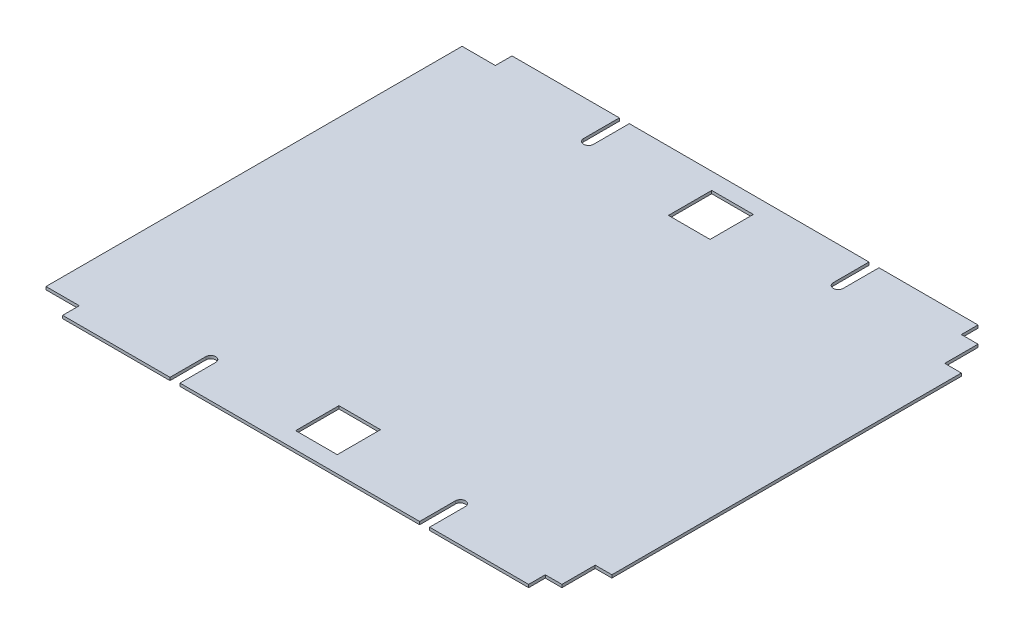
SolidWorks part; units mm, degrees
ref_plane "Front Plane" through (0, 0, 0) normal (0, 0, 1) x (1, 0, 0)
ref_plane "Top Plane" through (0, 0, 0) normal (0, 1, 0) x (1, 0, 0)
ref_plane "Right Plane" through (0, 0, 0) normal (1, 0, 0) x (0, 0, -1)
sketch "Sketch1" plane through (0, 0, 0) normal (0, 1, 0) x (1, 0, 0)
  line L1 (-280, 270) -> (280, 270)
  line L2 (-320, 250) -> (-320, -250)
  line L3 (-280, -270) -> (280, -270)
  line L4 (320, 250) -> (320, -250)
  line L5 (-280, 253.125) -> (280, -253.125) construction
  line L6 (-280, -253.125) -> (280, 253.125) construction
  line L9 (-320, 250) -> (-280, 250)
  line L10 (-280, 270) -> (-280, 250)
  line L13 (320, 250) -> (280, 250)
  line L14 (280, 270) -> (280, 250)
  line L17 (320, -250) -> (280, -250)
  line L18 (280, -270) -> (280, -250)
  line L21 (-320, -250) -> (-280, -250)
  line L22 (-280, -270) -> (-280, -250)
  point P0 (0, 0)
  dimension "D2" = 540
  dimension "D3" = 40
  dimension "D4" = 20
  dimension "D5" = 20
  dimension "D6" = 40
  dimension "D7" = 40
  dimension "D8" = 20
  dimension "D9" = 20
  dimension "D10" = 40
  dimension "D11" = 640
extrude "Boss-Extrude1" add sketch "Sketch1" along normal blind 3.5
sketch "Sketch2" plane through (0, 3.5, 0) normal (0, 1, 0) x (1, 0, 0)
  line L0 (-280, -270) -> (280, -270) construction
  line L1 (30, -250) -> (-20, -250)
  line L2 (30, -250) -> (30, -198)
  line L3 (30, -198) -> (-20, -198)
  line L4 (-20, -250) -> (-20, -198)
  line L6 (280, 270) -> (-280, 270) construction
  line L7 (-20, 198) -> (30, 198)
  line L8 (-20, 198) -> (-20, 250)
  line L9 (-20, 250) -> (30, 250)
  line L10 (30, 198) -> (30, 250)
  line L12 (320, -250) -> (320, 250) construction
  line L14 (320, 250) -> (300, 250)
  line L15 (320, 250) -> (320, 210)
  line L16 (320, 210) -> (300, 210)
  line L17 (300, 250) -> (300, 210)
  line L18 (320, -250) -> (300, -250)
  line L19 (320, -250) -> (320, -210)
  line L20 (320, -210) -> (300, -210)
  line L21 (300, -250) -> (300, -210)
  dimension "D1" = 52
  dimension "D2" = 50
  dimension "D3" = 20
  dimension "D4" = 290
  dimension "D5" = 50
  dimension "D6" = 52
  dimension "D7" = 20
  dimension "D8" = 290
  dimension "D9" = 40
  dimension "D10" = 20
  dimension "D11" = 40
  dimension "D12" = 20
extrude "Cut-Extrude1" cut sketch "Sketch2" against normal blind 10
sketch "Sketch3" plane through (0, 3.5, 0) normal (0, 1, 0) x (1, 0, 0)
  line L0 (300, 250) -> (300, 210) construction
  line L1 (280, 270) -> (-280, 270) construction
  line L2 (320, 0) -> (0, 0) construction
  line L4 (149, 227) -> (149, 270)
  line L5 (149, 270) -> (161, 270)
  line L6 (161, 227) -> (161, 270)
  line L7 (320, -210) -> (320, 210) construction
  line L8 (5, 198) -> (5, -198) construction
  line L9 (-20, 198) -> (30, 198) construction
  line L10 (30, -198) -> (-20, -198) construction
  line L11 (161, -227) -> (161, -270)
  line L12 (149, -270) -> (161, -270)
  line L13 (149, -227) -> (149, -270)
  line L14 (-139, -227) -> (-139, -270)
  line L15 (-139, -270) -> (-151, -270)
  line L16 (-151, -227) -> (-151, -270)
  line L17 (-151, 227) -> (-151, 270)
  line L18 (-139, 270) -> (-151, 270)
  line L19 (-139, 227) -> (-139, 270)
  arc A0 (149, 227) -> (161, 227) centre (155, 227) ccw
  arc A1 (149, -227) -> (161, -227) centre (155, -227) cw
  arc A2 (-139, -227) -> (-151, -227) centre (-145, -227) ccw
  arc A3 (-139, 227) -> (-151, 227) centre (-145, 227) cw
  dimension "D1" = 145
  dimension "D2" = 43
  dimension "D3" = 12
extrude "Cut-Extrude2" cut sketch "Sketch3" against normal blind 10
